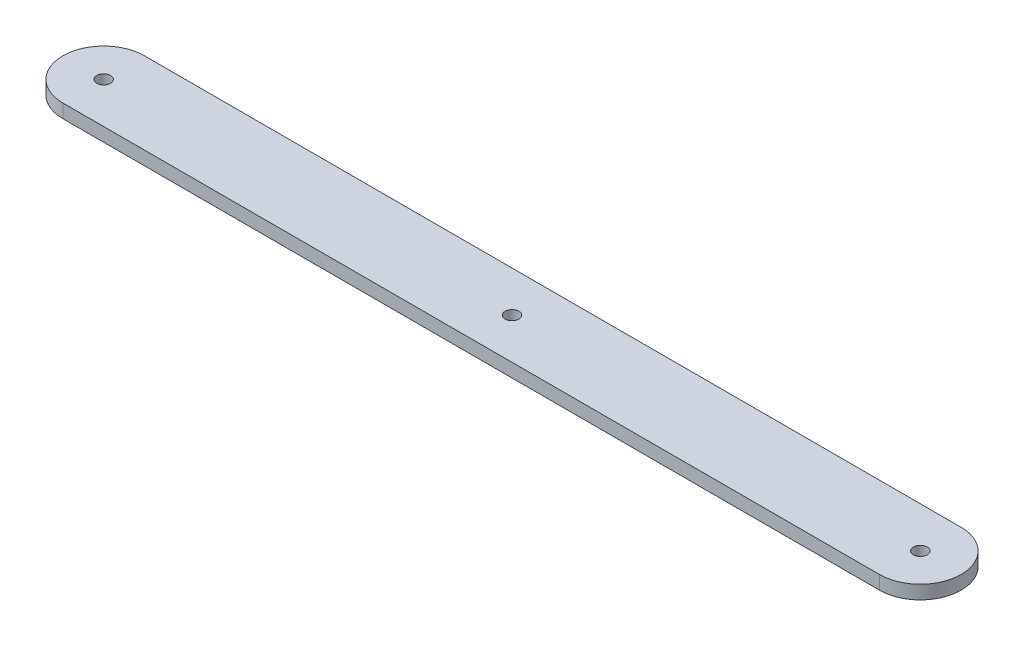
SolidWorks part; units mm, degrees
ref_plane "Front Plane" through (0, 0, 0) normal (0, 0, 1) x (1, 0, 0)
ref_plane "Top Plane" through (0, 0, 0) normal (0, 1, 0) x (1, 0, 0)
ref_plane "Right Plane" through (0, 0, 0) normal (1, 0, 0) x (0, 0, -1)
sketch "Sketch1" plane through (0, 0, 0) normal (0, 1, 0) x (1, 0, 0)
  line L0 (-95.25, 0) -> (95.25, 0) construction
  line L1 (-95.25, 9.525) -> (95.25, 9.525)
  line L2 (-95.25, -9.525) -> (95.25, -9.525)
  arc A0 (-95.25, 9.525) -> (-95.25, -9.525) centre (-95.25, 0) ccw
  arc A1 (95.25, -9.525) -> (95.25, 9.525) centre (95.25, 0) ccw
  circle A2 centre (95.25, 0) radius 2.5797 construction
  circle A3 centre (-95.25, 0) radius 2.5797 construction
  circle A4 centre (0, 0) radius 2.5797 construction
  point P3 (0, 0)
  dimension "D2" = 9.525
  dimension "D3" = 5.1594
  dimension "D1" = 190.5
extrude "Boss-Extrude1" add sketch "Sketch1" along normal blind 3.175
hole_wizard "M3 Clearance Hole1" positions "Sketch2" profile "Sketch3" hole size "M3" standard "ANSI Metric" end condition through all
sketch "Sketch2" plane through (0, 3.175, 0) normal (0, 1, 0) x (1, 0, 0)
  line L0 (95.25, 0) -> (-95.25, 0) construction
  point P0 (-95.25, 0)
  point P2 (0, 0)
  point P5 (95.25, 0)
  dimension "D1" = 190.5
sketch "Sketch3" plane through (-95.25, 3.175, 0) normal (1, 0, 0) x (0, 0, 1)
  line L0 (0, 0) -> (0, 3.175)
  line L1 (0, 3.175) -> (1.6, 3.175)
  line L2 (1.6, 3.175) -> (1.6, 0)
  line L5 (1.6, 0) -> (0, 0)
  line L11 (0, -6.35) -> (0, 107.95) construction
  dimension "Thru Hole Dia." = 3.2
  dimension "Thru Hole Depth" = 3.175
